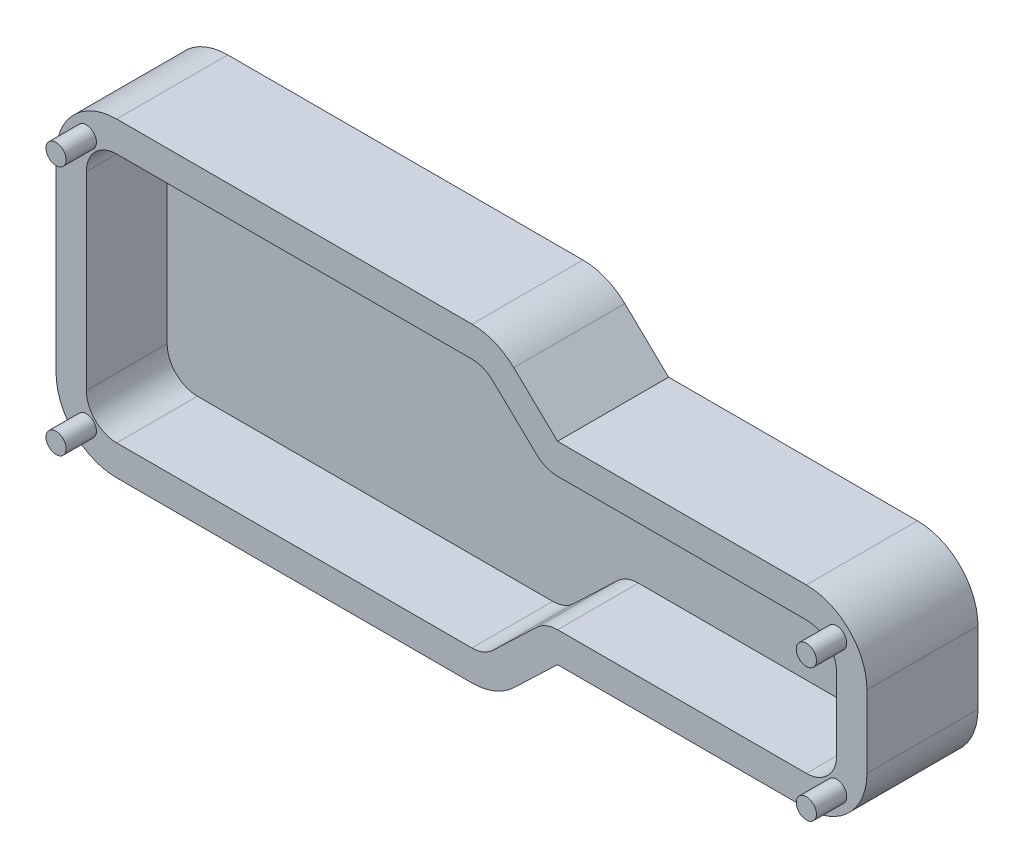
SolidWorks part; units mm, degrees
ref_plane "Front Plane" through (0, 0, 0) normal (0, 0, 1) x (1, 0, 0)
ref_plane "Top Plane" through (0, 0, 0) normal (0, 1, 0) x (1, 0, 0)
ref_plane "Right Plane" through (0, 0, 0) normal (1, 0, 0) x (0, 0, -1)
sketch "Sketch2" plane through (0, 0, 0) normal (0, 0, 1) x (1, 0, 0)
  line L0 (-34.29, 10.16) -> (0, 10.16)
  line L1 (-34.29, 10.16) -> (-34.29, 0)
  line L2 (-34.29, 0) -> (0, 0)
  line L3 (0, 10.16) -> (0, 0)
  line L4 (-69.31, 13.97) -> (-36.29, 13.97)
  line L5 (-69.31, 13.97) -> (-69.31, -3.81)
  line L6 (-69.31, -3.81) -> (-36.29, -3.81)
  line L7 (-36.29, 13.97) -> (-36.29, -3.81)
  line L8 (-31.29, 10.16) -> (-31.29, 0)
  line L9 (-71.31, 15.97) -> (-34.29, 15.97)
  line L10 (-34.29, 15.97) -> (-34.29, 12.16)
  line L11 (-34.29, 12.16) -> (-31.29, 12.16)
  line L12 (-31.29, 12.16) -> (-31.29, -2)
  line L13 (-31.29, -2) -> (-34.29, -2)
  line L14 (-34.29, -2) -> (-34.29, -5.81)
  line L15 (-34.29, -5.81) -> (-71.31, -5.81)
  line L16 (-71.31, -5.81) -> (-71.31, 15.97)
  point P4 (-34.29, 5.08)
  point P5 (-36.29, 5.08)
  dimension "D1" = 2
  dimension "D2" = 2
  dimension "D3" = 2
  dimension "D5" = 2
  dimension "D4" = 2
  dimension "D6" = 0
  dimension "pcb_overflow" = 2
  dimension "arduino_length" = 33.02
  dimension "arduino_width" = 17.78
  dimension "imu_header" = 3
  dimension "imu_length" = 34.29
  dimension "imu_width" = 10.16
sketch "Sketch3" plane through (0, 0, 0) normal (0, 0, 1) x (1, 0, 0)
  line L0 (-69.81, 17.47) -> (-34.6251, 17.47)
  line L1 (-32.5518, 16.6383) -> (-28.2152, 12.4917)
  line L2 (-26.1419, 11.66) -> (-1.5, 11.66)
  line L3 (1.5, 8.66) -> (1.5, 1.5)
  line L4 (-1.5, -1.5) -> (-26.1419, -1.5)
  line L5 (-28.2152, -2.3317) -> (-32.5518, -6.4783)
  line L6 (-34.6251, -7.31) -> (-69.81, -7.31)
  line L7 (-72.81, -4.31) -> (-72.81, 14.47)
  line L8 (-71.31, 15.97) -> (-34.29, 15.97) construction
  line L9 (-34.29, -5.81) -> (-71.31, -5.81) construction
  line L11 (-34.29, 0) -> (0, 0) construction
  line L12 (0, 10.16) -> (0, 0) construction
  line L13 (-71.31, -5.81) -> (-71.31, 15.97) construction
  line L14 (-69.81, 20.47) -> (-34.6251, 20.47)
  line L15 (-30.4785, 18.8066) -> (-26.1419, 14.66)
  line L16 (-26.1419, 14.66) -> (-1.5, 14.66)
  line L17 (4.5, 8.66) -> (4.5, 1.5)
  line L18 (-1.5, -4.5) -> (-26.1419, -4.5)
  line L19 (-26.1419, -4.5) -> (-30.4785, -8.6466)
  line L20 (-34.6251, -10.31) -> (-69.81, -10.31)
  line L21 (-75.81, -4.31) -> (-75.81, 14.47)
  arc A0 (-69.81, -7.31) -> (-72.81, -4.31) centre (-69.81, -4.31) cw
  arc A1 (-1.5, 11.66) -> (1.5, 8.66) centre (-1.5, 8.66) cw
  arc A2 (1.5, 1.5) -> (-1.5, -1.5) centre (-1.5, 1.5) cw
  arc A3 (-32.5518, -6.4783) -> (-34.6251, -7.31) centre (-34.6251, -4.31) cw
  arc A4 (-26.1419, -1.5) -> (-28.2152, -2.3317) centre (-26.1419, -4.5) ccw
  arc A5 (-28.2152, 12.4917) -> (-26.1419, 11.66) centre (-26.1419, 14.66) ccw
  arc A6 (-34.6251, 17.47) -> (-32.5518, 16.6383) centre (-34.6251, 14.47) cw
  arc A7 (-69.81, 17.47) -> (-72.81, 14.47) centre (-69.81, 14.47) ccw
  arc A8 (-34.6251, 20.47) -> (-30.4785, 18.8066) centre (-34.6251, 14.47) cw
  arc A9 (-26.1419, 14.66) -> (-26.1419, 14.66) centre (-26.1419, 14.66) ccw
  arc A10 (-1.5, 14.66) -> (4.5, 8.66) centre (-1.5, 8.66) cw
  arc A11 (4.5, 1.5) -> (-1.5, -4.5) centre (-1.5, 1.5) cw
  arc A12 (-26.1419, -4.5) -> (-26.1419, -4.5) centre (-26.1419, -4.5) ccw
  arc A13 (-30.4785, -8.6466) -> (-34.6251, -10.31) centre (-34.6251, -4.31) cw
  arc A14 (-69.81, -10.31) -> (-75.81, -4.31) centre (-69.81, -4.31) cw
  arc A15 (-69.81, 20.47) -> (-75.81, 14.47) centre (-69.81, 14.47) ccw
  circle A16 centre (-72.81, 17.47) radius 1
  circle A17 centre (-72.81, -7.31) radius 1
  circle A18 centre (1.5, -1.5) radius 1
  circle A19 centre (1.5, 11.66) radius 1
  point P26 (-33.4216, -7.31)
  point P29 (-27.3454, -1.5)
  point P32 (-27.3454, 11.66)
  point P35 (-33.4216, 17.47)
  dimension "D5" = 3
  dimension "D6" = 2
  dimension "D1" = 1.5
  dimension "D2" = 1.5
  dimension "D3" = 1.5
  dimension "D4" = 1.5
  dimension "gap_from_case" = 1.5
  dimension "case_slope_length" = 6
  dimension "case_thickness" = 3
  dimension "notch_dia" = 2
extrude "Boss-Extrude2" add sketch "Sketch3" along normal blind 8 and the other way blind 3
sketch "Sketch5" plane through (0, 0, -3) normal (0, 0, -1) x (-1, 0, 0)
  line L0 (-1.5, 1.5) -> (-1.5, 8.66) construction
  line L1 (26.1419, -1.5) -> (1.5, -1.5) construction
  line L2 (32.5518, -6.4783) -> (28.2152, -2.3317) construction
  line L3 (69.81, -7.31) -> (34.6251, -7.31) construction
  line L4 (72.81, 14.47) -> (72.81, -4.31) construction
  line L5 (-1.5, 1.5) -> (-1.5, 8.66)
  line L6 (26.1419, -1.5) -> (1.5, -1.5)
  line L7 (32.5518, -6.4783) -> (28.2152, -2.3317)
  line L8 (72.81, -4.31) -> (72.81, 14.47)
  line L9 (34.6251, -7.31) -> (69.81, -7.31)
  line L10 (28.2152, -2.3317) -> (32.5518, -6.4783)
  line L11 (1.5, -1.5) -> (26.1419, -1.5)
  line L12 (-1.5, 8.66) -> (-1.5, 1.5)
  line L13 (26.1419, 11.66) -> (1.5, 11.66)
  line L14 (32.5518, 16.6383) -> (28.2152, 12.4917)
  line L15 (69.81, 17.47) -> (34.6251, 17.47)
  line L16 (72.81, -4.31) -> (72.81, 14.47)
  line L17 (34.6251, -7.31) -> (69.81, -7.31)
  line L18 (28.2152, -2.3317) -> (32.5518, -6.4783)
  line L19 (1.5, -1.5) -> (26.1419, -1.5)
  line L20 (-1.5, 8.66) -> (-1.5, 1.5)
  line L21 (26.1419, 11.66) -> (1.5, 11.66)
  line L22 (32.5518, 16.6383) -> (28.2152, 12.4917)
  line L23 (69.81, 17.47) -> (34.6251, 17.47)
  line L24 (69.81, -7.31) -> (34.6251, -7.31)
  line L25 (72.81, 14.47) -> (72.81, -4.31)
  arc A0 (1.5, 11.66) -> (-1.5, 8.66) centre (1.5, 8.66) ccw construction
  arc A1 (-1.5, 1.5) -> (1.5, -1.5) centre (1.5, 1.5) ccw construction
  arc A2 (28.2152, -2.3317) -> (26.1419, -1.5) centre (26.1419, -4.5) ccw construction
  arc A3 (32.5518, -6.4783) -> (34.6251, -7.31) centre (34.6251, -4.31) ccw construction
  arc A4 (69.81, -7.31) -> (72.81, -4.31) centre (69.81, -4.31) ccw construction
  arc A5 (72.81, 14.47) -> (69.81, 17.47) centre (69.81, 14.47) ccw construction
  arc A6 (1.5, 11.66) -> (-1.5, 8.66) centre (1.5, 8.66) ccw
  arc A7 (-1.5, 1.5) -> (1.5, -1.5) centre (1.5, 1.5) ccw
  arc A8 (69.81, -7.31) -> (72.81, -4.31) centre (69.81, -4.31) ccw
  arc A9 (32.5518, -6.4783) -> (34.6251, -7.31) centre (34.6251, -4.31) ccw
  arc A10 (28.2152, -2.3317) -> (26.1419, -1.5) centre (26.1419, -4.5) ccw
  arc A11 (-1.5, 1.5) -> (1.5, -1.5) centre (1.5, 1.5) ccw
  arc A12 (1.5, 11.66) -> (-1.5, 8.66) centre (1.5, 8.66) ccw
  arc A13 (26.1419, 11.66) -> (28.2152, 12.4917) centre (26.1419, 14.66) ccw
  arc A14 (34.6251, 17.47) -> (32.5518, 16.6383) centre (34.6251, 14.47) ccw
  arc A15 (72.81, 14.47) -> (69.81, 17.47) centre (69.81, 14.47) ccw
  arc A16 (69.81, -7.31) -> (72.81, -4.31) centre (69.81, -4.31) ccw
  arc A17 (32.5518, -6.4783) -> (34.6251, -7.31) centre (34.6251, -4.31) ccw
  arc A18 (28.2152, -2.3317) -> (26.1419, -1.5) centre (26.1419, -4.5) ccw
  arc A19 (-1.5, 1.5) -> (1.5, -1.5) centre (1.5, 1.5) ccw
  arc A20 (1.5, 11.66) -> (-1.5, 8.66) centre (1.5, 8.66) ccw
  arc A21 (26.1419, 11.66) -> (28.2152, 12.4917) centre (26.1419, 14.66) ccw
  arc A22 (34.6251, 17.47) -> (32.5518, 16.6383) centre (34.6251, 14.47) ccw
  arc A23 (72.81, 14.47) -> (69.81, 17.47) centre (69.81, 14.47) ccw
  arc A24 (28.2152, -2.3317) -> (26.1419, -1.5) centre (26.1419, -4.5) ccw
  arc A25 (32.5518, -6.4783) -> (34.6251, -7.31) centre (34.6251, -4.31) ccw
  arc A26 (69.81, -7.31) -> (72.81, -4.31) centre (69.81, -4.31) ccw
  arc A27 (72.81, 14.47) -> (69.81, 17.47) centre (69.81, 14.47) ccw
  line M17 (72.81, 14.47) -> (72.81, -4.31)
  arc M18 (72.81, -4.31) -> (69.81, -7.31) centre (69.81, -4.31) cw
  line M19 (69.81, -7.31) -> (34.6251, -7.31)
  arc M20 (34.6251, -7.31) -> (32.5518, -6.4783) centre (34.6251, -4.31) cw
  line M21 (32.5518, -6.4783) -> (28.2152, -2.3317)
  arc M22 (28.2152, -2.3317) -> (26.1419, -1.5) centre (26.1419, -4.5) ccw
  line M23 (26.1419, -1.5) -> (1.5, -1.5)
  arc M24 (1.5, -1.5) -> (-1.5, 1.5) centre (1.5, 1.5) cw
  line M25 (-1.5, 1.5) -> (-1.5, 8.66)
  arc M26 (-1.5, 8.66) -> (1.5, 11.66) centre (1.5, 8.66) cw
  line M27 (1.5, 11.66) -> (26.1419, 11.66)
  arc M28 (26.1419, 11.66) -> (28.2152, 12.4917) centre (26.1419, 14.66) ccw
  line M29 (28.2152, 12.4917) -> (32.5518, 16.6383)
  arc M30 (32.5518, 16.6383) -> (34.6251, 17.47) centre (34.6251, 14.47) cw
  line M31 (34.6251, 17.47) -> (69.81, 17.47)
  arc M32 (69.81, 17.47) -> (72.81, 14.47) centre (69.81, 14.47) cw
  dimension "D1" = 0
extrude "Boss-Extrude3" add sketch "Sketch5" against normal blind 3 contours M17 M32 M31 M30 M29 M28 M27 M26 M25 M24 M23 M22 M21 M20 M19 M18 region at (-41.0126, 5.08, -3)
sketch "Sketch7" plane through (0, 0, 8) normal (0, 0, 1) x (1, 0, 0)
  circle A0 centre (-72.81, 17.47) radius 1 construction
  circle A1 centre (-72.81, 17.47) radius 1
  circle A2 centre (1.5, -1.5) radius 1 construction
  circle A3 centre (1.5, -1.5) radius 1
  circle A4 centre (1.5, 11.66) radius 1 construction
  circle A5 centre (1.5, 11.66) radius 1
  circle A6 centre (-72.81, -7.31) radius 1 construction
  circle A7 centre (-72.81, -7.31) radius 1
extrude "Boss-Extrude4" add sketch "Sketch7" against normal blind 11 and the other way blind 3
equation "\"D5@Sketch2\"=\"pcb_overflow\""
equation "\"D1@Sketch2\"=\"pcb_overflow\""
equation "\"D2@Sketch2\"=\"pcb_overflow\""
equation "\"D4@Sketch2\"=\"pcb_overflow\""
equation "\"D3@Sketch2\"=\"pcb_overflow\""
equation "\"D1@Sketch3\"=\"gap_from_case\""
equation "\"D2@Sketch3\"=\"gap_from_case\""
equation "\"D3@Sketch3\"=\"gap_from_case\""
equation "\"D4@Sketch3\"=\"gap_from_case\""
equation "\"D6@Sketch3\"=\"notch_dia\""
